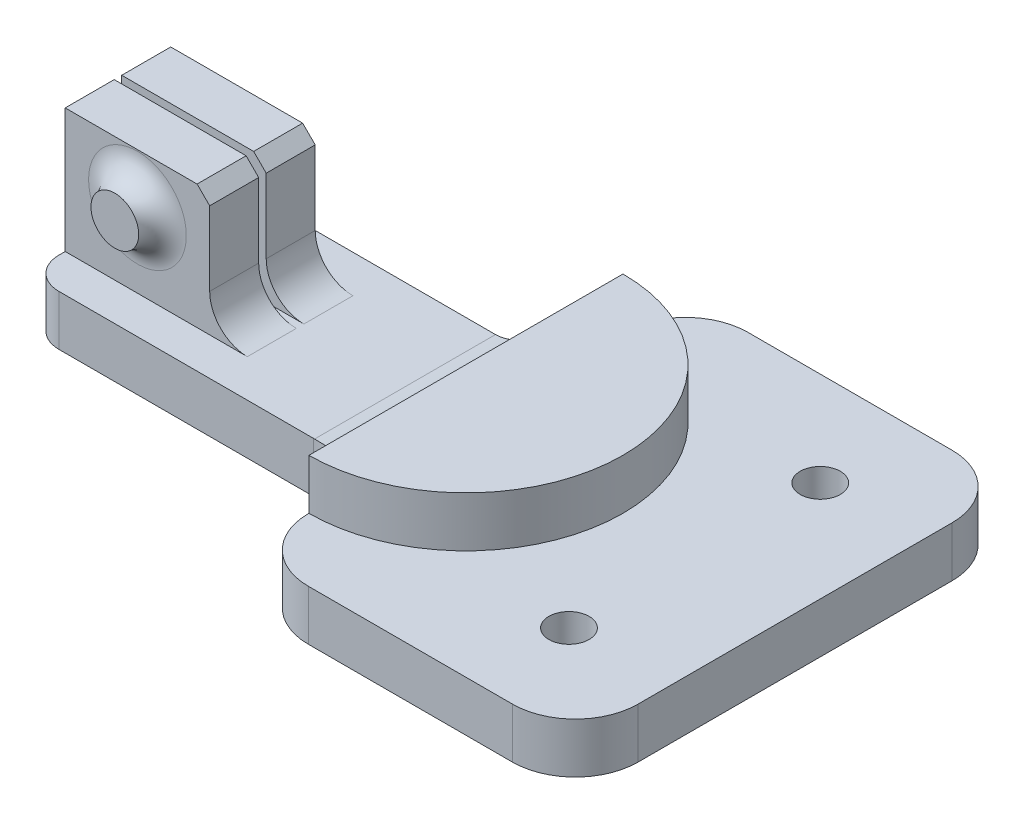
SolidWorks part; units mm, degrees
ref_plane "Alzado" through (0, 0, 0) normal (0, 0, 1) x (1, 0, 0)
ref_plane "Planta" through (0, 0, 0) normal (0, 1, 0) x (1, 0, 0)
ref_plane "Vista lateral" through (0, 0, 0) normal (1, 0, 0) x (0, 0, -1)
sketch "Croquis1" plane through (0, 0, 0) normal (0, 1, 0) x (1, 0, 0)
  line L1 (0, 0) -> (54, 0)
  line L2 (0, 0) -> (0, 35)
  line L3 (0, 35) -> (54, 35)
  line L4 (54, 0) -> (54, 35)
  circle A0 centre (46, 27.5) radius 1.6
  circle A1 centre (46, 7.5) radius 1.6
  dimension "D2" = 3.2
  dimension "D3" = 20
  dimension "D1" = 35
  dimension "D4" = 7.5
  dimension "D5" = 8
  dimension "D6" = 54
extrude "Saliente-Extruir1" add sketch "Croquis1" along normal blind 3
sketch "Croquis3" plane through (0, 3, 0) normal (0, 1, 0) x (1, 0, 0)
  line L0 (0, 35) -> (0, 0) construction
  line L1 (0, 17.3) -> (11.5, 17.3)
  line L2 (0, 17.3) -> (0, 13.4)
  line L3 (0, 13.4) -> (11.5, 13.4)
  line L4 (11.5, 17.3) -> (11.5, 13.4)
  line L5 (54, 35) -> (0, 35) construction
  line L6 (0, 21.8) -> (11.5, 21.8)
  line L7 (0, 21.8) -> (0, 17.9)
  line L8 (0, 17.9) -> (11.5, 17.9)
  line L9 (11.5, 21.8) -> (11.5, 17.9)
  dimension "D1" = 11.5
  dimension "D2" = 11.5
  dimension "D3" = 3.9
  dimension "D4" = 3.9
  dimension "D5" = 0.6
  dimension "D6" = 13.2
extrude "Saliente-Extruir2" add sketch "Croquis3" along normal blind 9.9
sketch "Croquis4" plane through (0, 0, -13.4) normal (0, 0, 1) x (1, 0, 0)
  line L0 (11.5, 12.9) -> (11.5, 3) construction
  line L1 (0, 3) -> (11.5, 3) construction
  circle A0 centre (5.75, 8.9) radius 1.9
  dimension "D3" = 3.8
  dimension "D1" = 5.75
  dimension "D2" = 5.9
extrude "Saliente-Extruir3" add sketch "Croquis4" along normal blind 1.8
sketch "Croquis5" plane through (0, 0, -21.8) normal (0, 0, -1) x (-1, 0, 0)
  circle A0 centre (-5.75, 8.9) radius 1.9 construction
  circle A1 centre (-5.75, 8.9) radius 1.9
extrude "Saliente-Extruir4" add sketch "Croquis5" along normal blind 1.8
fillet "Redondeo1" radius 2 2 edges at (7.65, 8.9, -21.8) (3.85, 8.9, -13.4)
fillet "Redondeo2" radius 3 2 edges at (11.5, 3, -19.85) (11.5, 3, -15.35)
sketch "Croquis6" plane through (0, 3, 0) normal (0, 1, 0) x (1, 0, 0)
  line L0 (54, 17.5) -> (0, 17.6) construction
  line L1 (54, 0) -> (54, 35) construction
  line L3 (27.75, 30.0486) -> (27.75, 5.0486)
  line L4 (0, 17.9) -> (0, 17.3) construction
  arc A0 (27.75, 5.0486) -> (27.75, 30.0486) centre (27.75, 17.5486) ccw
  dimension "D1" = 25
  dimension "D2" = 26.25
extrude "Saliente-Extruir5" add sketch "Croquis6" along normal blind 4
sketch "Croquis7" plane through (0, 3, 0) normal (0, 1, 0) x (1, 0, 0)
  line L0 (27.75, 30.0486) -> (27.75, 5.0486) construction
  line L1 (0, 35) -> (27.75, 35)
  line L2 (0, 35) -> (0, 24.8)
  line L3 (0, 24.8) -> (27.75, 24.8)
  line L4 (27.75, 35) -> (27.75, 24.8)
  line L5 (27.75, 30.0486) -> (27.75, 5.0486) construction
  line L6 (0, 0) -> (27.75, 0)
  line L7 (0, 0) -> (0, 10.4)
  line L8 (0, 10.4) -> (27.75, 10.4)
  line L9 (27.75, 0) -> (27.75, 10.4)
  line L10 (0, 13.4) -> (11.5, 13.4) construction
  line L11 (14.5, 21.8) -> (0, 21.8) construction
  dimension "D1" = 3
  dimension "D2" = 3
extrude "Cortar-Extruir1" cut sketch "Croquis7" against normal up to surface (3 mm away) up to face at (46, 0, -25.9)
chamfer "Chaflán1" distance 1 angle 45 2 edges at (11.5, 12.9, -15.35) (11.5, 12.9, -19.85)
fillet "Redondeo3" radius 5 7 edges at (27.75, 1.5, -24.8) (27.75, 1.5, -10.4) (27.75, 3, -17.6) (54, 1.5, -35) (54, 1.5, 0) (27.75, 1.5, -35) (27.75, 1.5, 0)
fillet "Redondeo4" radius 2.5 2 edges at (0, 1.5, -24.8) (0, 1.5, -10.4)
sketch "Croquis8" plane through (0, 0, 0) normal (0, -1, 0) x (1, 0, 0)
  line L8 (0, -12.9) -> (0, -22.3)
  line L9 (2.5, -24.8) -> (22.75, -24.8)
  line L10 (27.75, -29.8) -> (27.75, -30)
  line L11 (32.75, -35) -> (49, -35)
  line L12 (54, -30) -> (54, -5)
  line L13 (49, 0) -> (32.75, 0)
  line L14 (27.75, -5) -> (27.75, -5.4)
  line L15 (22.75, -10.4) -> (2.5, -10.4)
  line L16 (0, -12.9) -> (0, -22.3)
  line L17 (2.5, -24.8) -> (22.75, -24.8)
  line L18 (27.75, -29.8) -> (27.75, -30)
  line L19 (32.75, -35) -> (49, -35)
  line L20 (54, -30) -> (54, -5)
  line L21 (49, 0) -> (32.75, 0)
  line L22 (27.75, -5) -> (27.75, -5.4)
  line L23 (22.75, -10.4) -> (2.5, -10.4)
  circle A0 centre (46, -27.5) radius 1.6 construction
  circle A1 centre (46, -7.5) radius 1.6 construction
  circle A2 centre (46, -27.5) radius 1.6
  circle A3 centre (46, -7.5) radius 1.6
  arc A8 (0, -22.3) -> (2.5, -24.8) centre (2.5, -22.3) ccw
  arc A9 (27.75, -29.8) -> (22.75, -24.8) centre (22.75, -29.8) ccw
  arc A10 (27.75, -30) -> (32.75, -35) centre (32.75, -30) ccw
  arc A11 (49, -35) -> (54, -30) centre (49, -30) ccw
  arc A12 (54, -5) -> (49, 0) centre (49, -5) ccw
  arc A13 (32.75, 0) -> (27.75, -5) centre (32.75, -5) ccw
  arc A14 (22.75, -10.4) -> (27.75, -5.4) centre (22.75, -5.4) ccw
  arc A15 (2.5, -10.4) -> (0, -12.9) centre (2.5, -12.9) ccw
  arc A16 (0, -22.3) -> (2.5, -24.8) centre (2.5, -22.3) ccw
  arc A17 (27.75, -29.8) -> (22.75, -24.8) centre (22.75, -29.8) ccw
  arc A18 (27.75, -30) -> (32.75, -35) centre (32.75, -30) ccw
  arc A19 (49, -35) -> (54, -30) centre (49, -30) ccw
  arc A20 (54, -5) -> (49, 0) centre (49, -5) ccw
  arc A21 (32.75, 0) -> (27.75, -5) centre (32.75, -5) ccw
  arc A22 (22.75, -10.4) -> (27.75, -5.4) centre (22.75, -5.4) ccw
  arc A23 (2.5, -10.4) -> (0, -12.9) centre (2.5, -12.9) ccw
  dimension "D1" = 0
extrude "Saliente-Extruir6" add sketch "Croquis8" along normal blind 1
sketch "Croquis9" plane through (0, -1, 0) normal (0, -1, 0) x (1, 0, 0)
  line L0 (54, -30) -> (54, -5) construction
  line L1 (48.9, -5.8257) -> (46, -4.1514)
  line L2 (46, -4.1514) -> (43.1, -5.8257)
  line L3 (43.1, -5.8257) -> (43.1, -9.1743)
  line L4 (43.1, -9.1743) -> (46, -10.8486)
  line L5 (46, -10.8486) -> (48.9, -9.1743)
  line L6 (48.9, -9.1743) -> (48.9, -5.8257)
  line L7 (48.9, -25.8257) -> (46, -24.1514)
  line L8 (46, -24.1514) -> (43.1, -25.8257)
  line L9 (43.1, -25.8257) -> (43.1, -29.1743)
  line L10 (43.1, -29.1743) -> (46, -30.8486)
  line L11 (46, -30.8486) -> (48.9, -29.1743)
  line L12 (48.9, -29.1743) -> (48.9, -25.8257)
  circle A0 centre (46, -7.5) radius 2.9 construction
  circle A1 centre (46, -27.5) radius 2.9 construction
  dimension "D1" = 5.8
  dimension "D2" = 5.8
extrude "Cortar-Extruir2" cut sketch "Croquis9" against normal blind 0.5
